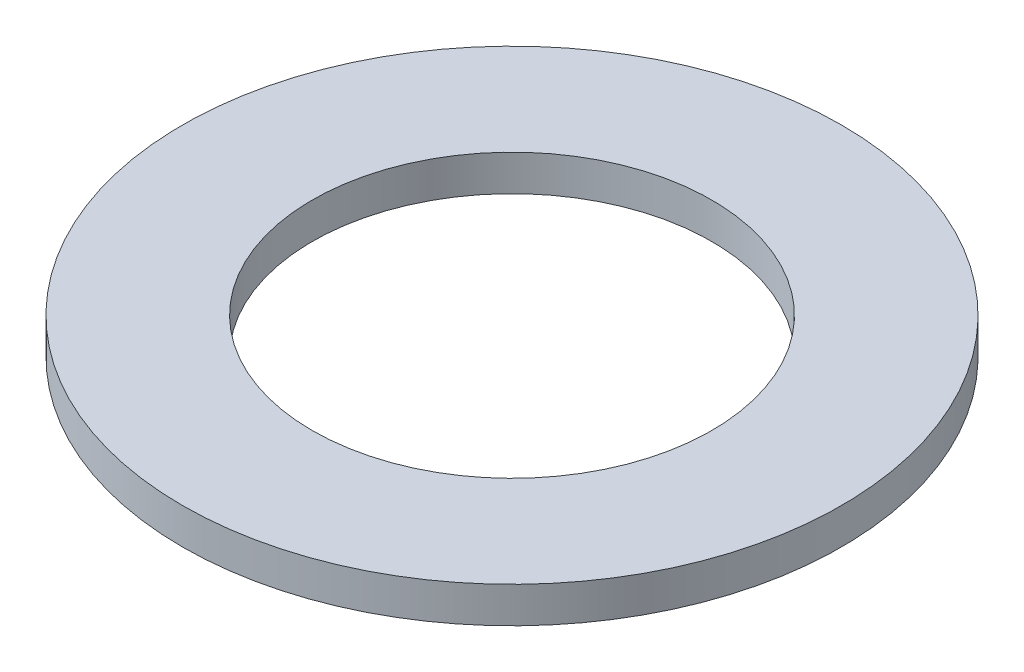
SolidWorks part; units mm, degrees
ref_plane "Front Plane" through (0, 0, 0) normal (0, 0, 1) x (1, 0, 0)
ref_plane "Top Plane" through (0, 0, 0) normal (0, 1, 0) x (1, 0, 0)
ref_plane "Right Plane" through (0, 0, 0) normal (1, 0, 0) x (0, 0, -1)
sketch "Sketch1" plane through (0, 0, 0) normal (0, 1, 0) x (1, 0, 0)
  circle A0 centre (0, 0) radius 82.5
  dimension "FLANGE_OD" = 165
extrude "Boss-Extrude1" add sketch "Sketch1" along normal blind 9
sketch "Sketch2" plane through (0, 0, 0) normal (0, 1, 0) x (1, 0, 0)
  circle A0 centre (0, 0) radius 50
  dimension "BORE_D" = 100
extrude "Cut-Extrude1" cut sketch "Sketch2" along normal through all
sketch "Sketch3" plane through (0, 9, 0) normal (0, 1, 0) x (1, 0, 0)
  circle A0 centre (0, 0) radius 37.9403 construction
  circle A1 centre (-37.9403, 0) radius 2.8616
  dimension "BOLT_D" = 5.7233
  dimension "BOLT_PCD" = 75.8806
extrude "Cut-Extrude2" cut sketch "Sketch3" against normal blind 6.8921 rebuild error yes
pattern_circular "CirPattern1" count 4 over 360 rebuild error yes
